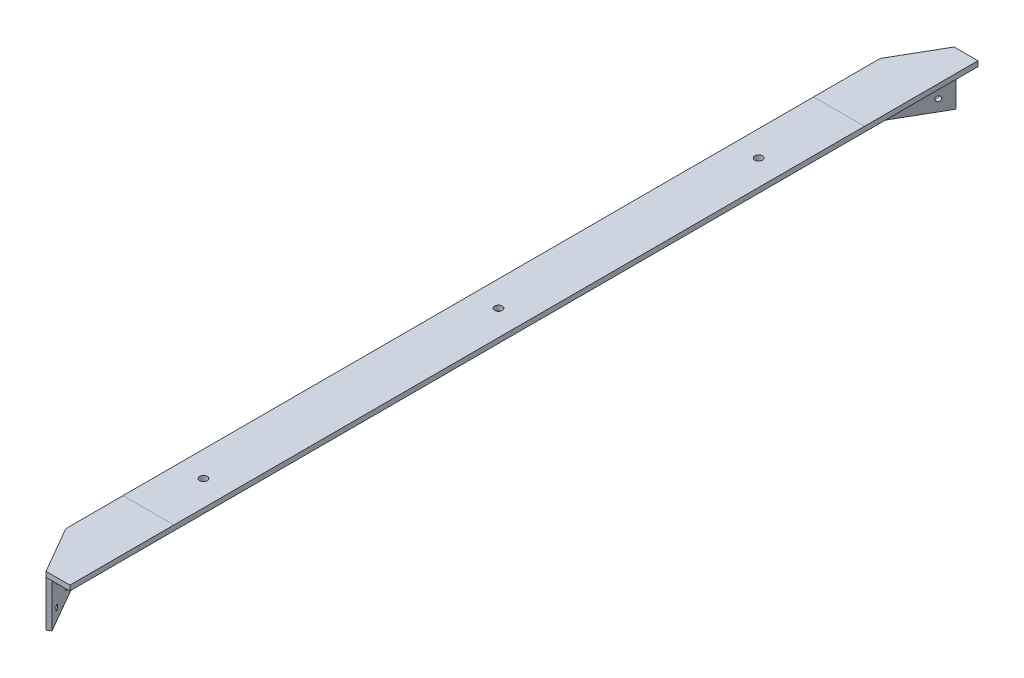
SolidWorks part; units mm, degrees
material "1.0116 (S235J2G3)"
ref_plane "Front Plane" through (0, 0, 0) normal (0, 0, 1) x (1, 0, 0)
ref_plane "Top Plane" through (0, 0, 0) normal (0, 1, 0) x (1, 0, 0)
ref_plane "Right Plane" through (0, 0, 0) normal (1, 0, 0) x (0, 0, -1)
sketch "Sketch1" plane through (0, 0, 0) normal (0, 0, 1) x (1, 0, 0)
  line L0 (-8, 8) -> (72, 8)
  line L1 (72, 8) -> (72, 0)
  line L2 (72, 0) -> (0, 0)
  line L3 (0, 0) -> (0, -72)
  line L4 (0, -72) -> (-8, -72)
  line L5 (-8, -72) -> (-8, 8)
  dimension "D1" = 80
  dimension "D2" = 80
  dimension "D3" = 8
  dimension "D4" = 8
extrude "Boss-Extrude1" add sketch "Sketch1" along normal blind 640
sketch "Sketch3" plane through (0, 0, 0) normal (0, 1, 0) x (1, 0, 0)
  line L0 (-8, -640) -> (34.5, -713.6122)
  line L1 (34.5, -713.6122) -> (72, -713.6122)
  line L2 (72, -713.6122) -> (72, -640)
  line L3 (72, -640) -> (-8, -640)
  line L4 (-8, -640) -> (-8, 0) construction
  dimension "D1" = 210
  dimension "D2" = 85
extrude "Boss-Extrude2" add sketch "Sketch3" along normal blind 8
sketch "Sketch4" plane through (0, 0, 0) normal (0, -1, 0) x (1, 0, 0)
  line L0 (-8, 640) -> (34.5, 713.6122)
  line L1 (34.5, 713.6122) -> (40.5, 710.1481)
  line L2 (40.5, 710.1481) -> (0, 640)
  line L3 (-8, 640) -> (0, 640) construction
  line L4 (0, 640) -> (-8, 640)
  dimension "D1" = 8
extrude "Boss-Extrude3" add sketch "Sketch4" along normal blind 72
sketch "Sketch6" plane through (-277.1281, 0, 160) normal (0.866, 0, -0.5) x (-0.5, 0, -0.866)
  line L0 (-635.2563, -36) -> (-554.2563, -36) construction
  line L1 (-635.2563, -72) -> (-635.2563, 0) construction
  line L2 (-554.2563, -72) -> (-554.2563, 0) construction
  line L3 (-594.7563, 0) -> (-594.7563, -72) construction
  line L4 (-554.2563, 0) -> (-635.2563, 0) construction
  line L5 (-554.2563, -72) -> (-635.2563, -72) construction
  circle A0 centre (-615.0063, -18) radius 4
  circle A1 centre (-574.5063, -18) radius 4
  circle A2 centre (-574.5063, -54) radius 4
  circle A3 centre (-615.0063, -54) radius 4
  dimension "D1" = 20.25
  dimension "D3" = 8
  dimension "D2" = 18
extrude "Cut-Extrude1" cut sketch "Sketch6" against normal blind 8
fillet "Fillet1" radius 10 2 edges at (-8, -32, 640) (0, -36, 640)
fillet "Fillet2" radius 8 3 edges at (0, 0, 318.6603) (0.3407, 0, 639.9087) (20.9199, 0, 676.2343)
mirror "Mirror1" about plane through (0, 0, 0) normal (0, 0, 1) of "Boss-Extrude1", "Boss-Extrude2", "Boss-Extrude3", "Cut-Extrude1", "Fillet1", "Fillet2"
sketch "Sketch7" plane through (0, 8, 0) normal (0, 1, 0) x (1, 0, 0)
  line L0 (-8, 535.2362) -> (72, 535.2362)
  line L1 (-8, -637.3205) -> (-8, 637.3205) construction
  line L2 (72, -713.6122) -> (72, 713.6122) construction
  line L3 (72, 535.2362) -> (72, -550.1105)
  line L4 (72, -550.1105) -> (-8, -550.1105)
  line L5 (-8, -550.1105) -> (-8, 535.2362)
  dimension "D1" = 102.0843
  dimension "D2" = 87.21
split line "Split Line1"
sketch "Sketch8" plane through (0, 8, 0) normal (0, 1, 0) x (1, 0, 0)
  line L0 (34.5, -713.6122) -> (72, -713.6122) construction
  line L1 (-8, -550.1105) -> (-8, 535.2362) construction
  line L2 (34.5, 713.6122) -> (72, 713.6122) construction
  circle A0 centre (32, 408.8899) radius 6
  circle A1 centre (32, 0) radius 6
  circle A2 centre (32, -463.6122) radius 6
  dimension "D1" = 12
  dimension "D2" = 12
  dimension "D3" = 12
  dimension "D4" = 250
  dimension "D5" = 40
  dimension "D6" = 40
  dimension "D7" = 40
  dimension "D8" = 304.7223
  dimension "D9" = 713.6122
extrude "Cut-Extrude2" cut sketch "Sketch8" against normal blind 8
